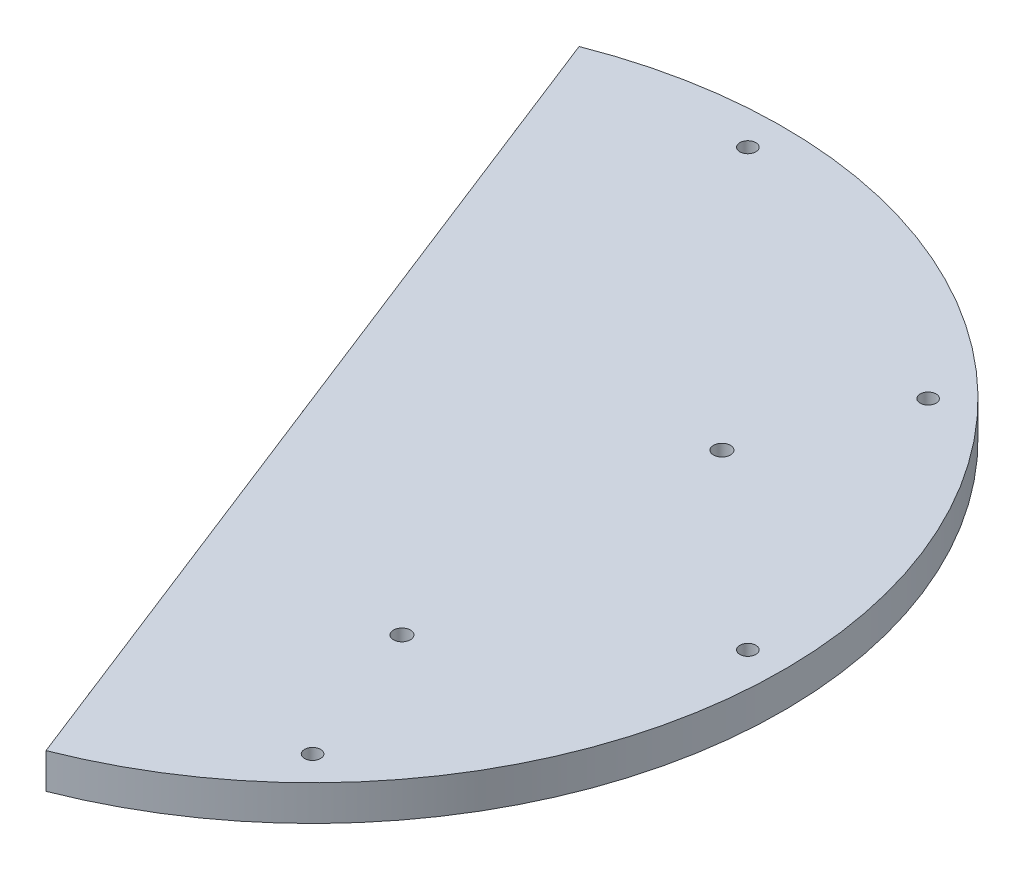
SolidWorks part; units mm, degrees
ref_plane "Front Plane" through (0, 0, 0) normal (0, 0, 1) x (1, 0, 0)
ref_plane "Top Plane" through (0, 0, 0) normal (0, 1, 0) x (1, 0, 0)
ref_plane "Right Plane" through (0, 0, 0) normal (1, 0, 0) x (0, 0, -1)
sketch "Sketch1" plane through (0, 0, 0) normal (0, 1, 0) x (1, 0, 0)
  circle A0 centre (0, 0) radius 100
  dimension "D1" = 200
extrude "Boss-Extrude1" add sketch "Sketch1" along normal blind 7.5
hole_wizard "CBORE for M3 SHCS1" positions "Sketch2" profile "Sketch3" counterbore size "M3" standard "ANSI Metric"
sketch "Sketch2" plane through (0, 0, 0) normal (0, -1, 0) x (-1, 0, 0)
  line L1 (0, -85) -> (0, -100) construction
  line L3 (0, 0) -> (0, -85) construction
  line L4 (0, 0) -> (0, 92.5) construction
  line L6 (0, 0) -> (92.5, 0) construction
  circle A0 centre (0, 0) radius 100 construction
  point P0 (0, -92.5)
  point P17 (-65.4074, -65.4074)
  point P18 (-92.5, 0)
  point P19 (-65.4074, 65.4074)
  point P20 (0, 92.5)
  point P21 (65.4074, 65.4074)
  point P22 (92.5, 0)
  point P23 (65.4074, -65.4074)
  dimension "D1" = 15
  dimension "D2" = 8
sketch "Sketch3" plane through (0, 0, 92.5) normal (1, 0, 0) x (0, 0, -1)
  line L0 (0, 0) -> (0, 8.5215)
  line L1 (0, 8.5215) -> (1.7, 7.5)
  line L2 (1.7, 7.5) -> (1.7, 3)
  line L3 (1.7, 3) -> (3.25, 3)
  line L4 (3.25, 3) -> (3.25, 0)
  line L5 (3.25, 0) -> (0, 0)
  line L10 (0, 8.5215) -> (-1.7, 7.5) construction
  line L11 (0, -6.35) -> (0, 107.95) construction
  dimension "Hole Dia." = 3.4
  dimension "Hole Depth" = 7.5
  dimension "C'Bore Dia." = 6.5
  dimension "C'Bore Depth" = 3
  dimension "Drill Angle" = 118
sketch "Sketch4" plane through (0, 0, 0) normal (0, 1, 0) x (1, 0, 0)
  line L0 (-53, -34) -> (-53, 34) construction
  line L1 (-53, 34) -> (53, 34) construction
  line L2 (53, 34) -> (53, -34) construction
  line L3 (53, -34) -> (-53, -34) construction
  line L4 (0, 34) -> (0, -34) construction
  point P8 (0, 0)
  dimension "D1" = 106
  dimension "D2" = 68
hole_wizard "CBORE for M3 SHCS2" positions "Sketch5" profile "Sketch6" counterbore size "M3" standard "ANSI Metric"
sketch "Sketch5" plane through (0, 0, 0) normal (0, -1, 0) x (-1, 0, 0)
  point P0 (-53, 34)
  point P3 (53, 34)
  point P6 (53, -34)
  point P9 (-53, -34)
sketch "Sketch6" plane through (53, 0, -34) normal (1, 0, 0) x (0, 0, -1)
  line L0 (0, 0) -> (0, 8.5815)
  line L1 (0, 8.5815) -> (1.8, 7.5)
  line L2 (1.8, 7.5) -> (1.8, 3)
  line L3 (1.8, 3) -> (3.25, 3)
  line L4 (3.25, 3) -> (3.25, 0)
  line L5 (3.25, 0) -> (0, 0)
  line L10 (0, 8.5815) -> (-1.8, 7.5) construction
  line L11 (0, -6.35) -> (0, 107.95) construction
  dimension "Hole Dia." = 3.6
  dimension "Hole Depth" = 7.5
  dimension "C'Bore Dia." = 6.5
  dimension "C'Bore Depth" = 3
  dimension "Drill Angle" = 118
sketch "Sketch8" plane through (0, 0, 0) normal (0, 1, 0) x (1, 0, 0)
  line L0 (-45.5873, 116.3907) -> (45.5873, -116.3907)
  point P2 (0, 0)
  dimension "D1" = 250
ref_plane "Plane1" through (0, 0, 0) normal (-0.9311, 0, 0.3647) x (0.3647, 0, 0.9311)
sketch "Sketch9" plane through (0, 0, 0) normal (-0.9311, 0, 0.3647) x (0.3647, 0, 0.9311)
  line L1 (-139.4421, 36.0587) -> (137.3978, 36.0587)
  line L2 (-139.4421, 36.0587) -> (-139.4421, -50.3959)
  line L3 (-139.4421, -50.3959) -> (137.3978, -50.3959)
  line L4 (137.3978, 36.0587) -> (137.3978, -50.3959)
extrude "Cut-Extrude1" cut sketch "Sketch9" along normal through all contours L1 L4 L3 L2
sketch "Sketch11" plane through (0, 0, 0) normal (-0.9311, 0, 0.3647) x (0.3647, 0, 0.9311)
  line L3 (0, 3.75) -> (-40, 3.75) construction
  line L4 (0, 7.5) -> (0, 0) construction
  circle A0 centre (0, 3.75) radius 1.875
  circle A1 centre (-40, 3.75) radius 1.875
  circle A2 centre (-80, 3.75) radius 1.875
  circle A3 centre (80, 3.75) radius 1.875
  circle A4 centre (40, 3.75) radius 1.875
  dimension "D1" = 3.75
  dimension "D5" = 40
  dimension "D4" = 3
extrude "Boss-Extrude3" add sketch "Sketch11" along normal blind 1.875
fillet "Fillet1" radius 1.875 5 edges at (-30.2379, 3.75, -72.0604) (-15.65, 3.75, -34.8154) (-1.0621, 3.75, 2.4297) (12.1583, 3.75, 36.183) (26.7462, 3.75, 73.428)
